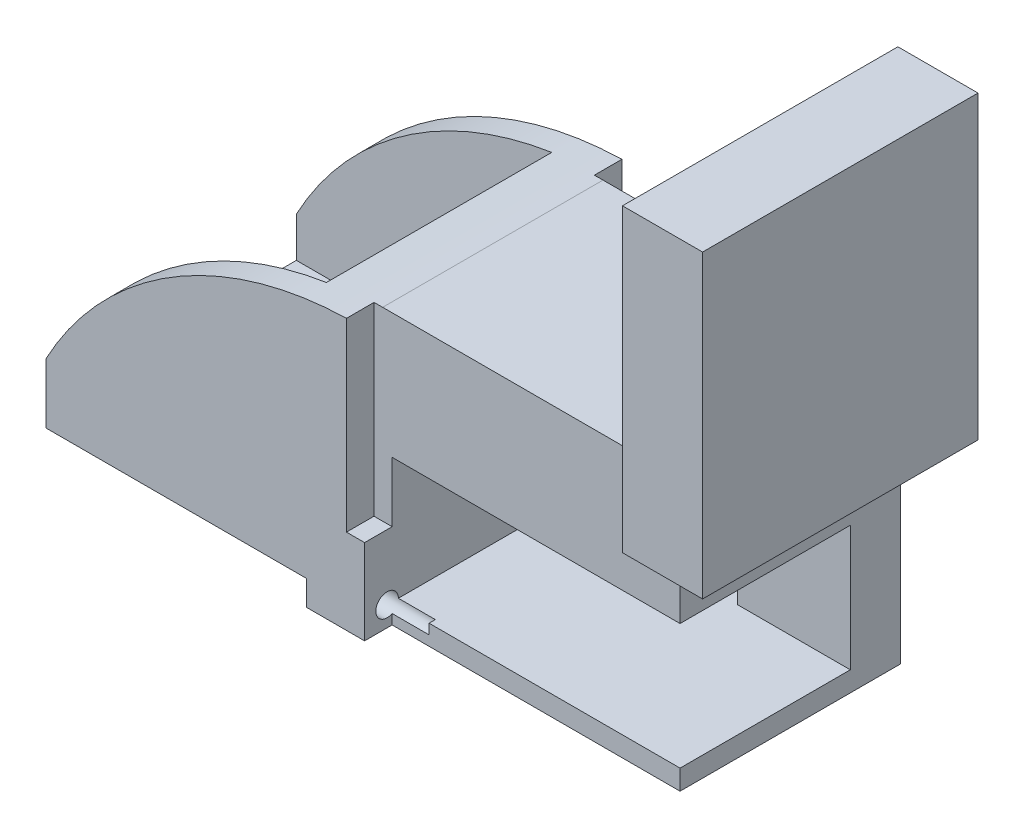
SolidWorks part; units mm, degrees
note: The reader was unsure of these and kept them because the rebuilt part matched: shared geometry of "Sketch10<6>".
other "Markup1"
sketch "Sketch8" plane through (15.28, 27, 11) normal (0.5774, 0.5773, 0.5774) x (0.7071, 0, -0.7071)
ref_plane "Front Plane" through (0, 0, 0) normal (0, 0, 1) x (1, 0, 0)
ref_plane "Top Plane" through (0, 0, 0) normal (0, 1, 0) x (1, 0, 0)
ref_plane "Right Plane" through (0, 0, 0) normal (1, 0, 0) x (0, 0, -1)
sketch "Sketch2" plane through (0, 0, 0) normal (0, 1, 0) x (1, 0, 0)
  line L1 (15.28, -11) -> (-15.28, -11)
  line L2 (15.28, -11) -> (15.28, 11)
  line L3 (15.28, 11) -> (-15.28, 11)
  line L4 (-15.28, -11) -> (-15.28, 11)
  line L5 (15.28, -11) -> (-15.28, 11) construction
  line L6 (15.28, 11) -> (-15.28, -11) construction
  point P0 (0, 0)
  dimension "D1" = 30.56
  dimension "D2" = 22
extrude "Boss-Extrude1" add sketch "Sketch2" along normal blind 27
sketch "Sketch4" plane through (0, 0, 11) normal (0, 0, 1) x (1, 0, 0)
  line L0 (15.28, 27) -> (15.28, 0) construction
  line L1 (15.28, 14.5) -> (-13.47, 14.5)
  line L2 (15.28, 14.5) -> (15.28, 2)
  line L3 (15.28, 2) -> (-13.47, 2)
  line L4 (-13.47, 14.5) -> (-13.47, 2)
  line L5 (-15.28, 0) -> (15.28, 0) construction
  dimension "D1" = 28.75
  dimension "D2" = 12.5
  dimension "D3" = 2
extrude "Cut-Extrude1" cut sketch "Sketch4" against normal blind 17 contours L1 L4 L3 L2
sketch "Sketch5" plane through (0, 0, -11) normal (0, 0, -1) x (-1, 0, 0)
  line L1 (-4.03, 14.5) -> (-0.03, 14.5)
  line L2 (-4.03, 14.5) -> (-4.03, 2)
  line L3 (-4.03, 2) -> (-0.03, 2)
  line L4 (-0.03, 14.5) -> (-0.03, 2)
  line L5 (5.47, 10) -> (9.47, 10)
  line L6 (5.47, 10) -> (5.47, 5)
  line L7 (5.47, 5) -> (9.47, 5)
  line L8 (9.47, 10) -> (9.47, 5)
  line L9 (-15.28, 2) -> (-15.28, 0) construction
  line L10 (-15.28, 2) -> (-15.28, 0)
  line L11 (-15.28, 14.5) -> (13.47, 14.5) construction
  line L12 (-15.28, 14.5) -> (13.47, 14.5)
  line L13 (13.47, 14.5) -> (13.47, 2) construction
  line L14 (13.47, 14.5) -> (13.47, 2)
  point P13 (7.47, 5)
  dimension "D1" = 6
  dimension "D2" = 4
  dimension "D3" = 5.5
  dimension "D4" = 3
  dimension "D5" = 5
  dimension "D6" = 4
extrude "Cut-Extrude2" cut sketch "Sketch5" against normal through all contours L4 L1 L2 L3 | L6 L7 L8 L5
sketch "Sketch9" plane through (-15.28, 0, 0) normal (-1, 0, 0) x (0, 0, 1)
  line L14 (-11, 0) -> (11, 0) construction
  line L15 (-13.75, 27) -> (13.75, 27)
  line L16 (-13.75, 27) -> (-13.75, 8.5)
  line L17 (-13.75, 8.5) -> (13.75, 8.5)
  line L18 (13.75, 27) -> (13.75, 8.5)
  line L19 (-11, 27) -> (11, 27) construction
  line L23 (11, 27) -> (11, 0) construction
  line L24 (-11, 27) -> (-11, 0) construction
  dimension "D1" = 8.5
  dimension "D2" = 2.75
  dimension "D3" = 2.75
extrude "Boss-Extrude2" add sketch "Sketch9" along normal blind 30
sketch "Sketch10" plane through (0, 8.5, 0) normal (0, -1, 0) x (1, 0, 0)
  line L0 (-45.28, 13.75) -> (-15.28, 13.75) construction
  line L5 (-45.28, -13.75) -> (-45.28, 13.75) construction
  line L6 (-45.28, 11.25) -> (-19.78, 11.25)
  line L7 (-45.28, 11.25) -> (-45.28, -11.25)
  line L8 (-45.28, -11.25) -> (-19.78, -11.25)
  line L9 (-19.78, 11.25) -> (-19.78, -11.25)
  line L12 (-15.28, 11) -> (-15.28, 13.75) construction
  line L13 (-15.28, 11) -> (-15.28, 13.75)
  line L15 (-17.78, 13.75) -> (-15.28, 13.75)
  line L16 (-17.78, 13.75) -> (-17.78, -13.75)
  line L17 (-17.78, -13.75) -> (-15.28, -13.75)
  line L18 (-15.28, 13.75) -> (-15.28, -13.75)
  line L19 (-45.28, 13.75) -> (-17.78, 13.75)
  line L20 (-45.28, -13.75) -> (-17.78, -13.75)
  point P18 (-45.28, 0)
  point P19 (-45.28, 0)
  line M5 (-45.28, 13.75) -> (-45.28, -13.75)
  line M11 (-15.28, 13.75) -> (-45.28, 13.75)
  line M12 (-45.28, -13.75) -> (-15.28, -13.75)
  dimension "D1" = 25.5
  dimension "D2" = 2.5
  dimension "D3" = 22.5
fillet "Fillet1" radius 35 7 edges at (-15.28, 27, 12.375) (-15.28, 27, -12.375) (-30.28, 27, 13.75) (-30.28, 27, -13.75) (-45.28, 17.75, 13.75) (-45.28, 27, 0) (-45.28, 17.75, -13.75)
extrude "Boss-Extrude3" add sketch "Sketch10" along normal blind 6 contours L16 L6 L9 L8 M11 M5 M12
extrude "Cut-Extrude3" cut sketch "Sketch10<6>" against normal through all contours L9 L6 L8 M5
sketch "Sketch10<6>" plane through (0, 8.5, 0) normal (0, -1, 0) x (1, 0, 0) same geometry as "Sketch10"
sketch "Sketch13" plane through (-19.78, 0, 0) normal (-1, 0, 0) x (0, 0, 1)
  line L0 (11.25, 2.5) -> (11.25, 26.5861) construction
  line L1 (-11.25, 2.5) -> (11.25, 2.5)
  line L2 (-11.25, 2.5) -> (-11.25, 4.5)
  line L3 (-11.25, 4.5) -> (11.25, 4.5)
  line L4 (11.25, 2.5) -> (11.25, 4.5)
  dimension "D1" = 2
extrude "Boss-Extrude4" add sketch "Sketch13" along normal up to vertex (25.5 mm away)
sketch "Sketch14" plane through (0, 4.5, 0) normal (0, 1, 0) x (1, 0, 0)
  line L0 (-45.28, 11.25) -> (-19.78, 11.25) construction
  line L1 (-19.78, -11.25) -> (-19.78, 11.25) construction
  circle A0 centre (-32.53, 0) radius 3.5
  point P5 (-32.53, 11.25)
  point P9 (-19.78, 0)
  dimension "D1" = 7
extrude "Cut-Extrude4" cut sketch "Sketch14" against normal through all contours A0
sketch "Sketch20" plane through (-15.28, 0, 0) normal (-1, 0, 0) x (0, 0, 1)
  line L0 (-11, 0) -> (11, 0) construction
  line L1 (9.75, 8.5) -> (13.75, 8.5)
  line L2 (9.75, 8.5) -> (9.75, 0)
  line L3 (9.75, 0) -> (13.75, 0)
  line L4 (13.75, 8.5) -> (13.75, 0)
  line L5 (13.75, 2.5) -> (13.75, 8.5) construction
  line L6 (0, -14.85) -> (0, 14.85) construction
  line L7 (-9.75, 0) -> (-13.75, 0)
  line L8 (-13.75, 8.5) -> (-13.75, 0)
  line L9 (-9.75, 8.5) -> (-13.75, 8.5)
  line L10 (-9.75, 8.5) -> (-9.75, 0)
  line L11 (11, 8.5) -> (13.75, 8.5) construction
  dimension "D1" = 4
extrude "Boss-Extrude13" add sketch "Sketch20" along normal blind 4 and the other way up to surface other way up to face at (-13.47, 8.25, 2.5)
sketch "Sketch15" plane through (-17.78, 0, 0) normal (1, 0, 0) x (0, 0, -1)
  line L0 (6, 2) -> (11, 2) construction
  line L1 (-13.75, 2.5) -> (-13.75, 8.5) construction
  circle A0 centre (-11.5, 2) radius 1.125
  dimension "D2" = 2.25
  dimension "D1" = 2.25
extrude "Cut-Extrude5" cut sketch "Sketch15" against normal blind 4 and the other way blind 8
mirror "Mirror3" about plane through (0, 0, 0) normal (0, 0, 1) of "Cut-Extrude5"
sketch "Sketch21" plane through (15.28, 0, 0) normal (1, 0, 0) x (0, 0, -1)
  line L0 (11, 27) -> (11, 0) construction
  line L1 (-11, 27) -> (11, 27)
  line L2 (-11, 27) -> (-11, 20.5)
  line L3 (-11, 20.5) -> (11, 20.5)
  line L4 (11, 27) -> (11, 20.5)
  line L5 (-11, 0) -> (11, 0) construction
  dimension "D1" = 20.5
extrude "Boss-Extrude14" add sketch "Sketch21" along normal blind 5
sketch "Sketch22" plane through (20.28, 0, 0) normal (1, 0, 0) x (0, 0, -1)
  line L1 (13.75, 20.5) -> (-13.75, 20.5)
  line L2 (13.75, 20.5) -> (13.75, 50.5)
  line L3 (13.75, 50.5) -> (-13.75, 50.5)
  line L4 (-13.75, 20.5) -> (-13.75, 50.5)
  line L6 (-11, 20.5) -> (11, 20.5) construction
  line L7 (-13.75, 26.9893) -> (-13.75, 8.5) construction
  line L8 (13.75, 26.9893) -> (13.75, 8.5) construction
  dimension "D1" = 30
extrude "Boss-Extrude15" add sketch "Sketch22" against normal blind 8
